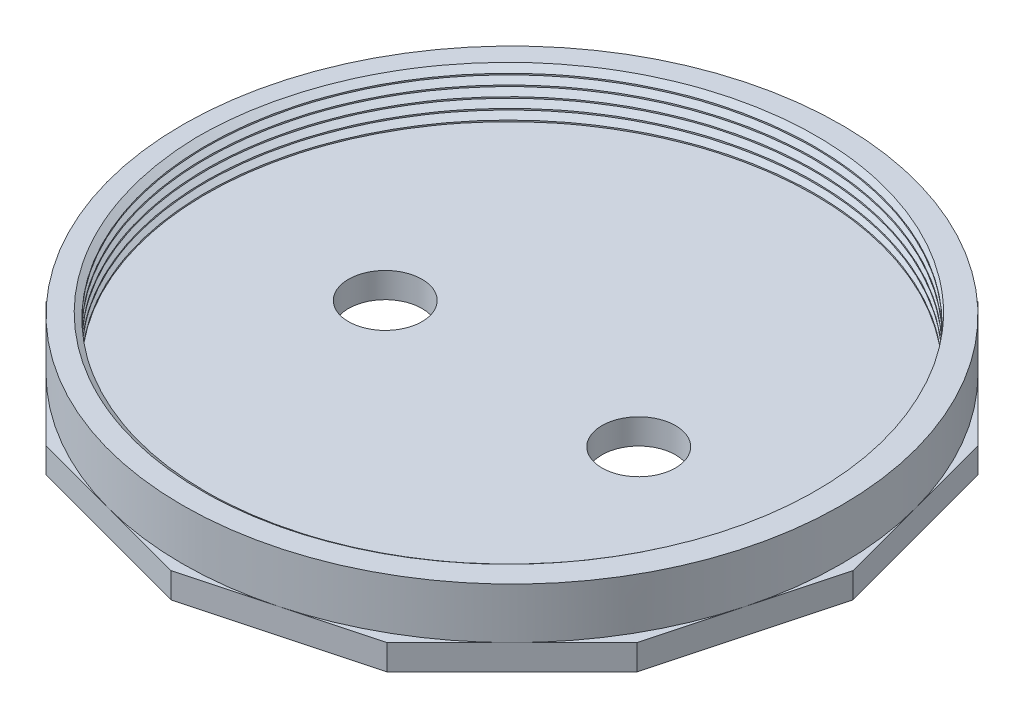
SolidWorks part; units mm, degrees
material "PET"
ref_plane "Front Plane" through (0, 0, 0) normal (0, 0, 1) x (1, 0, 0)
ref_plane "Top Plane" through (0, 0, 0) normal (0, 1, 0) x (1, 0, 0)
ref_plane "Right Plane" through (0, 0, 0) normal (1, 0, 0) x (0, 0, -1)
sketch "Sketch1" plane through (0, 0, 0) normal (0, 1, 0) x (1, 0, 0)
  circle A0 centre (0, 0) radius 60
  circle A1 centre (0, 0) radius 65
  dimension "D1" = 120
  dimension "D2" = 130
extrude "Boss-Extrude1" add sketch "Sketch1" along normal blind 10
sketch "Sketch2" plane through (0, 0, 0) normal (0, -1, 0) x (1, 0, 0)
  circle A0 centre (0, 0) radius 60
curve "Helix/Spiral1" pitch 2 height 10 turns 5
sketch "Sketch3" plane through (0, 0, 0) normal (1, 0, 0) x (0, 0, -1)
  line L1 (61.4944, 3.4958) -> (59.2444, 4.7948)
  line L2 (59.2444, 4.7948) -> (59.2444, 2.1968)
  line L3 (59.2444, 2.1968) -> (61.4944, 3.4958)
  circle A0 centre (59.9944, 3.4958) radius 0.75 construction
sweep "Cut-Sweep1" cut profiles "Sketch3" path "Helix/Spiral1" align with end faces yes
sketch "Sketch4" plane through (0, 0, 0) normal (0, -1, 0) x (1, 0, 0)
  circle A0 centre (0, 0) radius 65
extrude "Boss-Extrude2" add sketch "Sketch4" along normal blind 5
sketch "Sketch5" plane through (0, -5, 0) normal (0, -1, 0) x (1, 0, 0)
  line L1 (67.293, 0) -> (58.2774, 33.6465)
  line L2 (58.2774, 33.6465) -> (33.6465, 58.2774)
  line L3 (33.6465, 58.2774) -> (0, 67.293)
  line L4 (0, 67.293) -> (-33.6465, 58.2774)
  line L5 (-33.6465, 58.2774) -> (-58.2774, 33.6465)
  line L6 (-58.2774, 33.6465) -> (-67.293, 0)
  line L7 (-67.293, 0) -> (-58.2774, -33.6465)
  line L8 (-58.2774, -33.6465) -> (-33.6465, -58.2774)
  line L9 (-33.6465, -58.2774) -> (0, -67.293)
  line L10 (0, -67.293) -> (33.6465, -58.2774)
  line L11 (33.6465, -58.2774) -> (58.2774, -33.6465)
  line L12 (58.2774, -33.6465) -> (67.293, 0)
  circle A0 centre (0, 0) radius 65 construction
  circle A1 centre (0, 0) radius 64
extrude "Boss-Extrude3" add sketch "Sketch5" against normal blind 5
sketch "Sketch6" plane through (0, -5, 0) normal (0, -1, 0) x (1, 0, 0)
  line L1 (-25, 20) -> (25, 20)
  line L2 (-25, 20) -> (-25, -20)
  line L3 (-25, -20) -> (25, -20)
  line L4 (25, 20) -> (25, -20)
  line L5 (-25, 20) -> (25, -20) construction
  line L6 (-25, -20) -> (25, 20) construction
  circle A0 centre (-25, 0) radius 7.25
  circle A1 centre (25, 0) radius 7.25
  point P0 (0, 0)
  dimension "D3" = 14.5
  dimension "D4" = 14.5
  dimension "D1" = 40
  dimension "D2" = 50
extrude "Cut-Extrude1" cut sketch "Sketch6" against normal blind 10 contours A1 | A0
